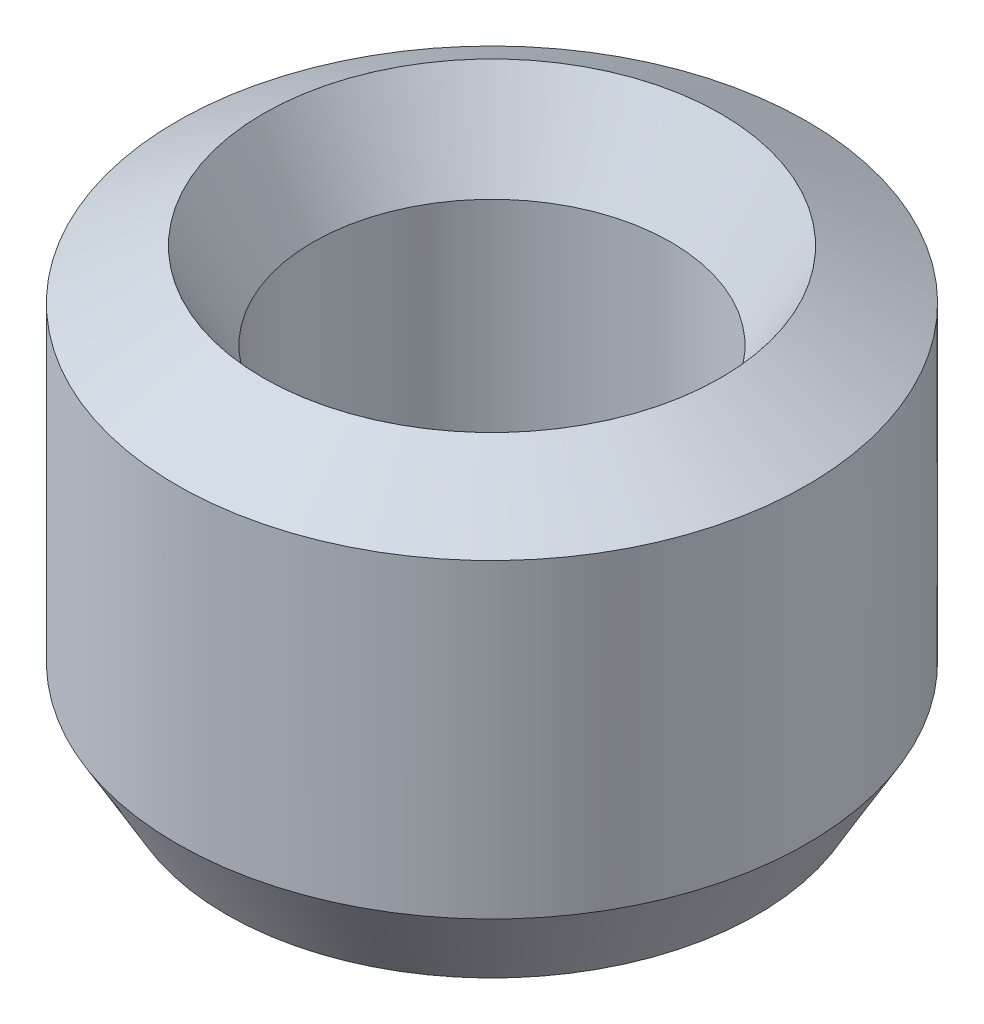
SolidWorks part; units mm, degrees
ref_plane "Front Plane" through (0, 0, 0) normal (0, 0, 1) x (1, 0, 0)
ref_plane "Top Plane" through (0, 0, 0) normal (0, 1, 0) x (1, 0, 0)
ref_plane "Right Plane" through (0, 0, 0) normal (1, 0, 0) x (0, 0, -1)
sketch "Sketch1" plane through (0, 0, 0) normal (0, 1, 0) x (1, 0, 0)
  circle A0 centre (0, 0) radius 25
  dimension "SLEEVE_OD" = 50
extrude "Boss-Extrude1" add sketch "Sketch1" along normal blind 35.4307
sketch "Sketch2" plane through (0, 0, 0) normal (0, 1, 0) x (1, 0, 0)
  circle A0 centre (0, 0) radius 14.1991
  dimension "BORE_D" = 28.3983
extrude "Cut-Extrude1" cut sketch "Sketch2" along normal through all
chamfer "Chamfer1" distance 3.9526 angle 60 4 edges at (0, 35.4307, 14.1991) (0, 0, 14.1991) (0, 0, 25) (0, 35.4307, 25) first distance on face at (0, 35.4307, 14.1991) first distance on face at (0, 0, 14.1991) first distance on face at (0, 35.4307, 25)
